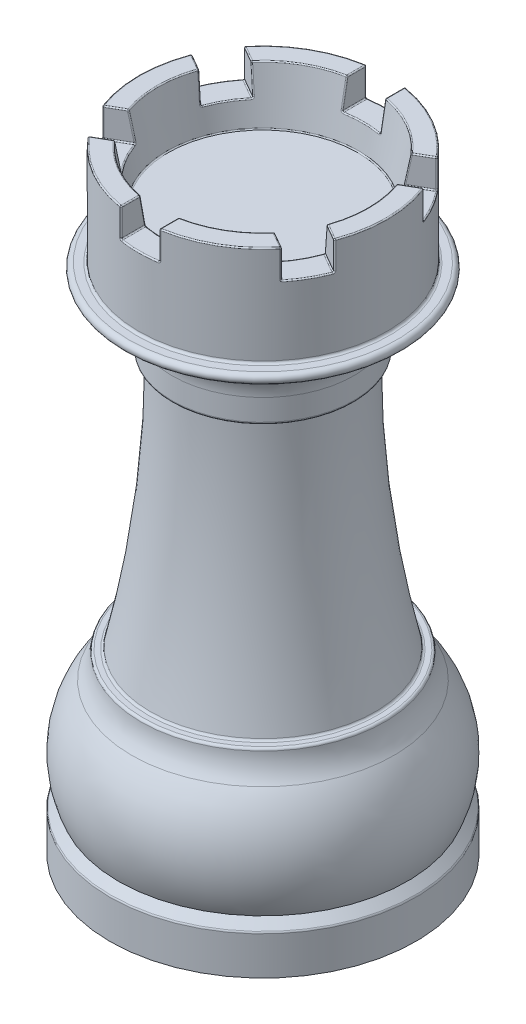
SolidWorks part; units mm, degrees
ref_plane "Front Plane" through (0, 0, 0) normal (0, 0, 1) x (1, 0, 0)
ref_plane "Top Plane" through (0, 0, 0) normal (0, 1, 0) x (1, 0, 0)
ref_plane "Right Plane" through (0, 0, 0) normal (1, 0, 0) x (0, 0, -1)
sketch "Sketch1" plane through (0, 0, 0) normal (0, 0, 1) x (1, 0, 0)
  line L0 (16, 4) -> (16, 0)
  line L1 (15.1036, 5) -> (15.9268, 4.1768)
  line L2 (9.5, 48) -> (9.5, 45.75)
  line L3 (13, 64) -> (13, 53.7813)
  line L4 (10.0302, 58.5) -> (0, 58.5)
  line L5 (13, 64) -> (11, 64)
  line L6 (14.0312, 53.5313) -> (13.25, 53.5313)
  line L7 (9.25, 45.5) -> (9, 45.5)
  line L8 (11, 64) -> (10.0302, 58.5)
  line L9 (16, 0) -> (0, 0)
  line L10 (12.5, 18.5) -> (12, 18.5)
  line L11 (0, 0) -> (0, 58.5)
  line L12 (0, 0) -> (0, -4.8979) construction
  arc A0 (16, 4) -> (15.9268, 4.1768) centre (15.75, 4) ccw
  arc A1 (15.1036, 5) -> (13.7193, 15.7192) centre (5.6068, 9.2226) ccw
  arc A2 (12.7496, 18.2633) -> (13.7193, 15.7192) centre (17.1905, 18.4991) ccw
  arc A3 (12.7496, 18.2633) -> (12.5, 18.5) centre (12.5, 18.25) ccw
  arc A4 (8.75, 45.2509) -> (11.7565, 18.6933) centre (124, 44.849) ccw
  arc A5 (9, 45.5) -> (8.75, 45.2509) centre (9, 45.25) ccw
  arc A6 (9.25, 45.5) -> (9.5, 45.75) centre (9.25, 45.75) ccw
  arc A7 (14.0312, 52.5312) -> (9.5, 48) centre (14.0312, 48) ccw
  arc A8 (14.0312, 52.5312) -> (14.0312, 53.5313) centre (14.0312, 53.0312) ccw
  arc A9 (13, 53.7813) -> (13.25, 53.5313) centre (13.25, 53.7813) ccw
  arc A10 (11.7565, 18.6933) -> (12, 18.5) centre (12, 18.75) ccw
  dimension "D3" = 0.25
  dimension "D4" = 5
  dimension "D5" = 4.4471
  dimension "D6" = 12
  dimension "D7" = 4.5312
  dimension "D8" = 0.5
  dimension "D9" = 0.25
  dimension "D10" = 10.3932
  dimension "D12" = 18.5
  dimension "D16" = 9.5
  dimension "D1" = 32
  dimension "D2" = 64
  dimension "D11" = 135
  dimension "D13" = 12.5
  dimension "D14" = 45.5
  dimension "D15" = 9
  dimension "D17" = 124
  dimension "D18" = 13
  dimension "D19" = 10
  dimension "D20" = 2
  dimension "D21" = 4
  dimension "D24" = 48
  dimension "D25" = 58.5
revolve "Revolve1" add sketch "Sketch1" angle 360 about L12
sketch "Sketch2" plane through (0, 64, 0) normal (0, 1, 0) x (1, 0, 0)
  line L0 (13.4647, 5.4644) -> (-11.4647, -8.9285)
  line L1 (-2, 14.393) -> (2, 14.393)
  line L2 (-2, 14.393) -> (-2, -14.393)
  line L3 (-2, -14.393) -> (2, -14.393)
  line L4 (2, 14.393) -> (2, -14.393)
  line L5 (-2, 14.393) -> (2, -14.393) construction
  line L6 (-2, -14.393) -> (2, 14.393) construction
  line L7 (11.4647, 8.9285) -> (13.4647, 5.4644)
  line L8 (11.4647, 8.9285) -> (-13.4647, -5.4644)
  line L9 (-13.4647, -5.4644) -> (-11.4647, -8.9285)
  line L10 (11.4647, -8.9285) -> (-13.4647, 5.4644)
  line L11 (13.4647, -5.4644) -> (11.4647, -8.9285)
  line L12 (13.4647, -5.4644) -> (-11.4647, 8.9285)
  line L13 (-11.4647, 8.9285) -> (-13.4647, 5.4644)
  line L14 (-2, -14.393) -> (-2, 14.393)
  line L15 (2, -14.393) -> (-2, -14.393)
  line L16 (2, -14.393) -> (2, 14.393)
  line L17 (2, 14.393) -> (-2, 14.393)
  line L18 (-13.4647, -5.4644) -> (11.4647, 8.9285)
  line L19 (-11.4647, -8.9285) -> (-13.4647, -5.4644)
  line L20 (-11.4647, -8.9285) -> (13.4647, 5.4644)
  line L21 (13.4647, 5.4644) -> (11.4647, 8.9285)
  line L22 (-11.4647, 8.9285) -> (13.4647, -5.4644)
  line L23 (-13.4647, 5.4644) -> (-11.4647, 8.9285)
  line L24 (-13.4647, 5.4644) -> (11.4647, -8.9285)
  line L25 (11.4647, -8.9285) -> (13.4647, -5.4644)
  circle A0 centre (0, 0) radius 14.5313 construction
  circle A1 centre (0, 0) radius 11 construction
  point P0 (0, 0)
  circle M2 centre (0, 0) radius 11
  circle M3 centre (0, 0) radius 13
  dimension "D2" = 6
extrude "Cut-Extrude3" cut sketch "Sketch2" against normal blind 3 contours L12 L10 M2 M3 | L2 L12 L10 L8 M2 | L12 L13 L10 M3 | L12 L0 L8 L4 M2 | L12 L0 L4 L10 M2 | L2 L10 L8 L0 M2 | L12 L10 M3 M2 | L11 L12 L10 M3 | L8 L0 M3 M2 | L7 L8 L0 M3 | L8 L0 M2 M3 | L8 L9 L0 M3 | L4 L10 L0 L2 M2 | L4 L2 M2 M3 | L4 L2 L3 M3 | L4 L1 L2 M3 | L4 L2 M3 M2 | L12 L8 L4 L2 M2 | L8 L12 L2 | L12 L4 L8 | L4 L12 L8 L2 L10 L0 | L10 L2 L8 | L10 L4 L0 | L0 L12 L4 | L0 L10 L2 | L4 L3 L2 L1 region at (11.8386, 64, -6.835) region at (10.3435, 64, -5.9718) region at (5.981, 64, -3.4531) region at (5.981, 64, 3.4531) region at (2.6667, 64, 0) region at (10.3435, 64, 5.9718) region at (11.8386, 64, 6.835) region at (0, 64, -13.67) region at (0, 64, -11.9436) region at (1.3333, 64, 2.3094) region at (0, 64, 0) region at (1.3333, 64, -2.3094) region at (0, 64, -6.9062) region at (0, 64, 6.9062) region at (-1.3333, 64, 2.3094) region at (-1.3333, 64, -2.3094) region at (0, 64, 11.9436) region at (0, 64, 13.67) region at (-11.8386, 64, -6.835) region at (-10.3435, 64, -5.9718) region at (-5.981, 64, 3.4531) region at (-2.6667, 64, 0) region at (-5.981, 64, -3.4531) region at (-10.3435, 64, 5.9718) region at (-11.8386, 64, 6.835)
fillet "Fillet1" radius 0.125 73 edges at (12.1243, 62.5, -4.6906) (10.1243, 62.5, -8.1547) (2, 62.5, -12.8452) (-2, 62.5, -12.8452) (-10.1243, 62.5, -8.1547) (-12.1243, 62.5, -4.6906) (-12.1243, 62.5, 4.6906) (-10.1243, 62.5, 8.1547) (-2, 62.5, 12.8452) (2, 62.5, 12.8452) (10.1243, 62.5, 8.1547) (12.1243, 62.5, 4.6906) (6.5, 64, -11.2583) (9.2459, 64, -7.6475) (2, 64, -11.8309) (-9.2459, 64, -7.6475) (-6.5, 64, -11.2583) (-2, 64, -11.8309) (-11.2459, 64, -4.1834) (-11.2459, 64, 4.1834) (-13, 64, 0) (-9.2459, 64, 7.6475) (-2, 64, 11.8309) (-6.5, 64, 11.2583) (9.2459, 64, 7.6475) (6.5, 64, 11.2583) (2, 64, 11.8309) (13, 64, 0) (11.2459, 64, 4.1834) (11.2459, 64, -4.1834) (11.0128, 61, -4.0488) (9.0128, 61, -7.5129) (11.2583, 61, -6.5) (2, 61, -11.5617) (-2, 61, -11.5617) (0, 61, -13) (-9.0128, 61, -7.5129) (-11.0128, 61, -4.0488) (-11.2583, 61, -6.5) (-11.0128, 61, 4.0488) (-9.0128, 61, 7.5129) (-11.2583, 61, 6.5) (-2, 61, 11.5617) (2, 61, 11.5617) (0, 61, 13) (9.0128, 61, 7.5129) (11.0128, 61, 4.0488) (11.2583, 61, 6.5) (-9.0682, 61, 5.2355) (-11, 64, 0) (-9.0682, 61, -5.2355) (-5.5, 64, -9.5263) (0, 61, -10.471) (5.5, 64, -9.5263) (9.0682, 61, -5.2355) (11, 64, 0) (9.0682, 61, 5.2355) (5.5, 64, 9.5263) (0, 61, 10.471) (-5.5, 64, 9.5263) (0, 58.5, 10.0302)
scale "Scale1" scale about origin uniform scaling yes scale factor 0.71875
sketch "Sketch3" plane through (0, 0, 0) normal (0, -1, 0) x (1, 0, 0)
  circle A0 centre (0, 0) radius 10.2
  dimension "D1" = 20.4
extrude "Cut-Extrude4" cut sketch "Sketch3" against normal blind 7
sketch "Sketch4" plane through (0, 7, 0) normal (0, -1, 0) x (1, 0, 0)
  circle A0 centre (0, 0) radius 4.4
  dimension "D1" = 8.8
extrude "Cut-Extrude5" [suppressed] cut sketch "Sketch4" against normal blind 5
sketch "Sketch5" [suppressed] plane through (0, 13, 0) normal (0, -1, 0) x (1, 0, 0)
  circle A0 centre (0, 0) radius 2.2
  dimension "D1" = 4.4
extrude "Cut-Extrude6" [suppressed] cut sketch "Sketch5" against normal blind 13
sketch "Sketch6" plane through (0, 0, 0) normal (0, 0, 1) x (1, 0, 0)
  line L0 (-10.75, 1) -> (0, 1)
  line L1 (-10.75, 1) -> (-10.75, 0)
  line L2 (-10.75, 0) -> (0, 0)
  line L3 (0, 0) -> (0, -1) construction
  line L4 (0, 0) -> (0, 1)
  dimension "D2" = 1
  dimension "D4" = 21.5
revolve "Cut-Revolve1" cut sketch "Sketch6" angle 360 about L3
sketch "Sketch7" plane through (0, 0, 0) normal (0, 0, 1) x (1, 0, 0)
  line L0 (0, 0) -> (-10.55, 0)
  line L1 (0, 0) -> (0, 1)
  line L2 (0, 1) -> (-10.55, 1)
  line L3 (-10.55, 0) -> (-10.55, 1)
  line L4 (0, 0) -> (0, -1.3413) construction
  line L5 (-10.75, 1) -> (10.75, 1) construction
  line L6 (0, 1) -> (0, 2)
  line L7 (0, 2) -> (-10, 2)
  line L8 (-10, 2) -> (-10, 1)
  dimension "D1" = 21.1
  dimension "D2" = 20
  dimension "D3" = 2
revolve "Base (Black Rook)" [suppressed] add sketch "Sketch7" angle 360 about L4
sketch "Sketch8" plane through (0, 0, 0) normal (0, 0, 1) x (1, 0, 0)
  line L0 (-10.2, 1) -> (10.2, 1) construction
  line L3 (0, 1) -> (-10.55, 1) construction
  line L4 (-10.55, 0) -> (-10.55, 1) construction
  line L5 (0, 0) -> (-10.55, 0) construction
  line L6 (0, 0) -> (0, 1) construction
  line L7 (0, 1) -> (0, 2.5)
  line L8 (0, 2.5) -> (-10, 2.5)
  line L9 (-10, 2.5) -> (-10, 1)
  line L10 (0, 1) -> (-10.55, 1)
  line L11 (-10.55, 0) -> (-10.55, 1)
  line L12 (0, 0) -> (-10.55, 0)
  line L13 (0, 0) -> (0, 1)
  line L14 (0, 0) -> (0, -0.8353) construction
  dimension "D1" = 20
  dimension "D3" = 2.5
revolve "Base (White Rook)" add sketch "Sketch8" angle 360 about L14 region at (-5, 1.75, 0) region at (-5.275, 0.5, 0)
equation "\"D1@Cut-Extrude5\"=\"SocketDepth\""
equation "\"D1@Sketch3\"=\"BaseOuterDiam\"+0.4"
equation "\"D1@Cut-Extrude4\"=6mm+1mm"
equation "\"D1@Cut-Extrude2\"=\"SocketDepth\""
equation "\"D1@Sketch4\"=\"SocketDiam\"+0.3"
equation "\"D1@Cut-Extrude3\"=3"
equation "\"D1@Cut-Extrude1\"=\"PawnHeight\"+\"MagThickness\"-\"FeltThickness\""
equation "\"D1@Sketch2\"=4"
equation "\"PawnHeight\"= 1mm"
equation "\"MagDiam\"= 12mm"
equation "\"MagThickness\"= 3mm"
equation "\"KnightHeight\"= 2.5mm"
equation "\"RookHeight\"= 4mm"
equation "\"BishopHeight\"= 5.5mm"
equation "\"QueenHeight\"= 6.5mm"
equation "\"KingHeight\"= 8mm"
equation "\"WeightOuterDiam\"= 18mm"
equation "\"WeightInnerDiam\"= \"MagDiam\" + 0.3mm"
equation "\"WeightHeight\"= 9mm"
equation "\"BaseOuterDiam\"= 20mm"
equation "\"BaseInnerDiam\"= 12.7mm"
equation "\"FeltThickness\"= 1mm"
equation "\"ThreadedDepth\"= 10mm"
equation "\"TapdrillDiam\"= 4.4mm"
equation "\"SocketDepth\"= 5mm"
equation "\"SocketDiam\"= 8.5mm"
equation "\"D1@Sketch6\"=\"SocketDiam\"+0.3"
equation "\"D1@Sketch7\"=21.1mm"
equation "\"D1@Sketch5\"=\"TapdrillDiam\""
equation "\"D1@Cut-Extrude6\"=\"ThreadedDepth\"+3mm"
